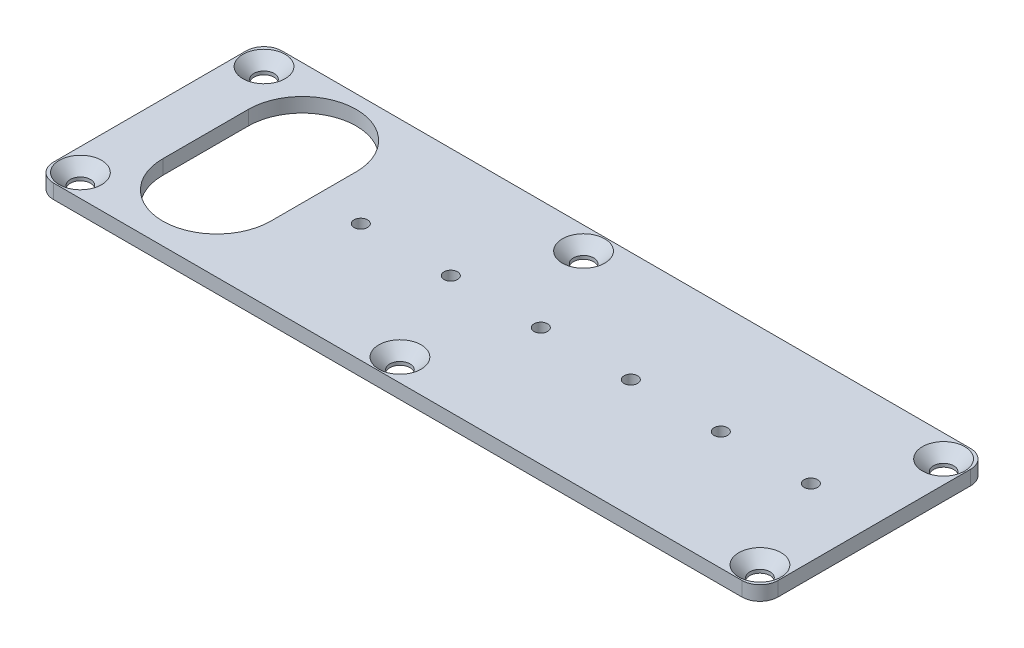
SolidWorks part; units mm, degrees
material "Acrylic (Medium-high impact)"
ref_plane "Front Plane" through (0, 0, 0) normal (0, 0, 1) x (1, 0, 0)
ref_plane "Top Plane" through (0, 0, 0) normal (0, 1, 0) x (1, 0, 0)
ref_plane "Right Plane" through (0, 0, 0) normal (1, 0, 0) x (0, 0, -1)
sketch "Sketch1" plane through (0, 0, 0) normal (0, 1, 0) x (1, 0, 0)
  line L1 (0, 0) -> (161, 0)
  line L2 (0, 0) -> (0, 50.8)
  line L3 (0, 50.8) -> (161, 50.8)
  line L4 (161, 0) -> (161, 50.8)
  dimension "D1" = 50.8
  dimension "D2" = 161
extrude "Boss-Extrude1" add sketch "Sketch1" along normal blind 3.2
sketch "Sketch2" plane through (0, 3.2, 0) normal (0, 1, 0) x (1, 0, 0)
  line L0 (161, 0) -> (161, 50.8) construction
  line L1 (23.5, 35.8) -> (23.5, 16.8) construction
  line L2 (161, 50.8) -> (0, 50.8) construction
  line L3 (35.5, 35.8) -> (35.5, 16.8)
  line L4 (11.5, 35.8) -> (11.5, 16.8)
  circle A0 centre (146, 26.3) radius 1.5
  circle A1 centre (126, 26.3) radius 1.5
  circle A2 centre (106, 26.3) radius 1.5
  circle A3 centre (86, 26.3) radius 1.5
  circle A4 centre (66, 26.3) radius 1.5
  circle A5 centre (46, 26.3) radius 1.5
  arc A6 (35.5, 35.8) -> (11.5, 35.8) centre (23.5, 35.8) ccw
  arc A7 (11.5, 16.8) -> (35.5, 16.8) centre (23.5, 16.8) ccw
  point P18 (23.5, 26.3)
  dimension "D1" = 3
  dimension "D2" = 15
  dimension "D3" = 24.5
  dimension "D4" = 20
  dimension "D5" = 20
  dimension "D6" = 20
  dimension "D7" = 20
  dimension "D8" = 20
  dimension "D9" = 24.5
  dimension "D10" = 24.5
  dimension "D11" = 24.5
  dimension "D12" = 24.5
  dimension "D13" = 24.5
  dimension "D14" = 149.5
  dimension "D15" = 125.5
  dimension "D16" = 19
  dimension "D17" = 15
extrude "Cut-Extrude2" cut sketch "Sketch2" against normal through all
fillet "Fillet1" radius 4 4 edges at (161, 1.6, 0) (0, 1.6, 0) (0, 1.6, -50.8) (161, 1.6, -50.8)
hole_wizard "CSK for M4 Flat Head Machine Screw1" positions "Sketch4" profile "Sketch3" countersink size "M4" standard "ANSI Metric"
sketch "Sketch4" plane through (0, 3.2, 0) normal (0, 1, 0) x (1, 0, 0)
  point P0 (156, 5)
  point P3 (76, 5)
  point P6 (5, 5)
  point P9 (5, 45.8)
  point P12 (76, 45.8)
  point P15 (156, 45.8)
sketch "Sketch3" plane through (156, 3.2, -5) normal (1, 0, 0) x (0, 0, 1)
  line L0 (0, 0) -> (0, 6.3519)
  line L1 (0, 6.3519) -> (2.25, 5)
  line L2 (2.25, 5) -> (2.25, 2.45)
  line L3 (2.25, 2.45) -> (4.7, 0)
  line L5 (4.7, 0) -> (0, 0)
  line L6 (-2.25, 2.45) -> (-4.7, 0) construction
  line L10 (0, 6.3519) -> (-2.25, 5) construction
  line L11 (0, -6.35) -> (0, 107.95) construction
  dimension "Hole Dia." = 4.5
  dimension "Hole Depth" = 5
  dimension "Near C'Sink Dia." = 9.4
  dimension "Near C'Sink Angle" = 90
  dimension "Drill Angle" = 118
